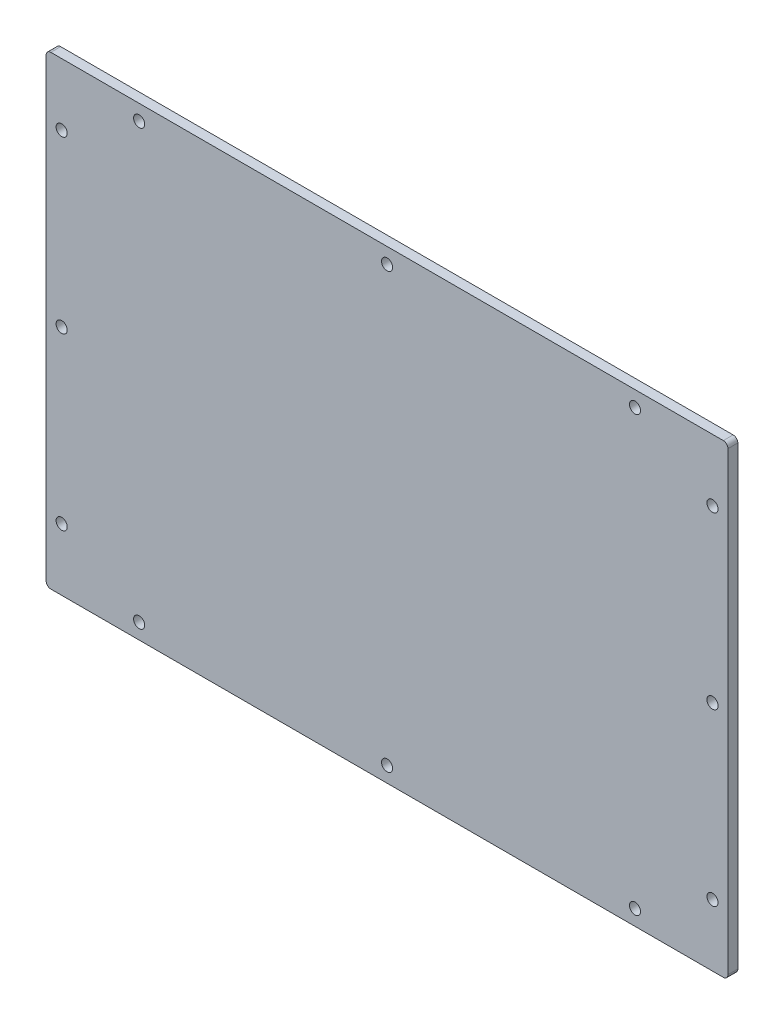
SolidWorks part; units mm, degrees
ref_plane "Front Plane" through (0, 0, 0) normal (0, 0, 1) x (1, 0, 0)
ref_plane "Top Plane" through (0, 0, 0) normal (0, 1, 0) x (1, 0, 0)
ref_plane "Right Plane" through (0, 0, 0) normal (1, 0, 0) x (0, 0, -1)
sketch "Sketch1" plane through (0, 0, 0) normal (0, 0, 1) x (1, 0, 0)
  line L0 (0, 0) -> (0, 75) construction
  line L1 (-110, -75) -> (110, -75)
  line L2 (-110, -75) -> (-110, 75)
  line L3 (-110, 75) -> (110, 75)
  line L4 (110, -75) -> (110, 75)
  line L5 (-110, -75) -> (110, 75) construction
  line L6 (-110, 75) -> (110, -75) construction
  line L15 (0, 0) -> (-110, 0) construction
  point P0 (0, 0)
  dimension "D1" = 220
  dimension "D2" = 150
extrude "Boss-Extrude1" add sketch "Sketch1" along normal blind 3.175 contours L3 L2 L1 L4 region at (0, 0, 0)
hole_wizard "M3 Clearance Hole1" positions "Sketch2" profile "Sketch3" hole size "M3" standard "ANSI Metric" end condition through all
sketch "Sketch2" plane through (0, 0, 3.175) normal (0, 0, 1) x (1, 0, 0)
  line L1 (-105, -70) -> (105, -70)
  line L2 (-105, -70) -> (-105, 70)
  line L3 (-105, 70) -> (105, 70)
  line L4 (105, -70) -> (105, 70)
  line L5 (-105, -70) -> (105, 70) construction
  line L6 (-105, 70) -> (105, -70) construction
  line L7 (-110, -75) -> (-110, 75) construction
  line L8 (-110, 75) -> (110, 75) construction
  point P2 (0, 0)
  point P113 (-80, 70)
  point P115 (80, 70)
  point P116 (0, 70)
  point P118 (-105, 55)
  point P120 (-105, 0)
  point P122 (-105, -55)
  point P124 (-80, -70)
  point P126 (0, -70)
  point P128 (80, -70)
  point P130 (105, -55)
  point P132 (105, 0)
  point P134 (105, 55)
  dimension "D1" = 5
  dimension "D2" = 5
  dimension "D3" = 80
  dimension "D4" = 80
  dimension "D5" = 55
  dimension "D6" = 55
sketch "Sketch3" plane through (0, 0, 3.175) normal (1, 0, 0) x (0, -1, 0)
  line L0 (0, 0) -> (0, 3.175)
  line L1 (0, 3.175) -> (1.8, 3.175)
  line L2 (1.8, 3.175) -> (1.8, 0)
  line L5 (1.8, 0) -> (0, 0)
  line L11 (0, -6.35) -> (0, 107.95) construction
  dimension "Thru Hole Dia." = 3.6
  dimension "Thru Hole Depth" = 3.175
sketch "Sketch4" plane through (0, 0, 3.175) normal (0, 0, 1) x (1, 0, 0)
  line L1 (-5, -5) -> (5, -5)
  line L2 (-5, -5) -> (-5, 5)
  line L3 (-5, 5) -> (5, 5)
  line L4 (5, -5) -> (5, 5)
  line L5 (-5, -5) -> (5, 5) construction
  line L6 (-5, 5) -> (5, -5) construction
  point P0 (0, 0)
  dimension "D1" = 10
  dimension "D2" = 10
extrude "Boss-Extrude2" add sketch "Sketch4" against normal through all
fillet "Fillet2" radius 1.5 4 edges at (-110, -75, 1.5875) (110, -75, 1.5875) (110, 75, 1.5875) (-110, 75, 1.5875)
